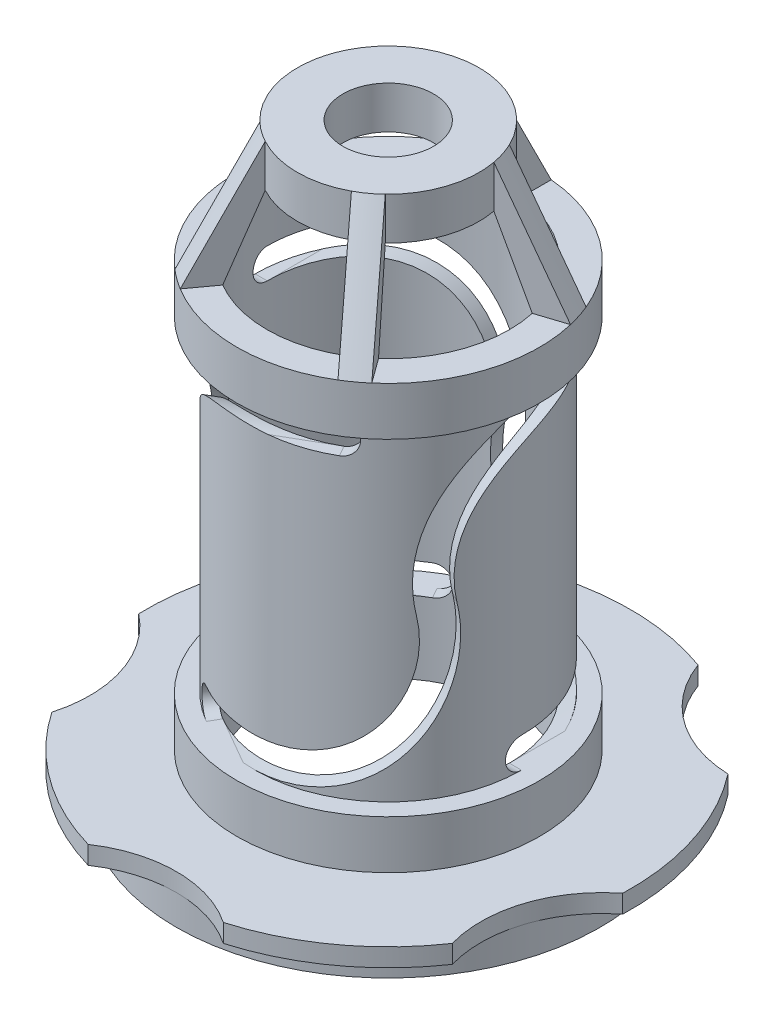
SolidWorks part; units mm, degrees
ref_plane "前视基准面" through (0, 0, 0) normal (0, 0, 1) x (1, 0, 0)
ref_plane "上视基准面" through (0, 0, 0) normal (0, 1, 0) x (1, 0, 0)
ref_plane "右视基准面" through (0, 0, 0) normal (1, 0, 0) x (0, 0, -1)
other "Configuration Table"
sketch "草图1" plane through (0, 0, 0) normal (0, 0, 1) x (1, 0, 0)
  line L0 (0, 74.4543) -> (0, -61.1877) construction
  line L2 (35, -49) -> (35, -44)
  line L3 (35, -44) -> (40, -44)
  line L4 (40, -44) -> (40, -41)
  line L5 (40, -41) -> (25, -41)
  line L9 (20, -49) -> (20, 29)
  line L11 (7.5, 49) -> (7.5, 42)
  line L14 (15, 49) -> (7.5, 49)
  line L18 (25, 29) -> (25, 21)
  line L19 (25, 21) -> (22, 21)
  line L20 (22, 21) -> (22, -33)
  line L21 (22, -33) -> (25, -33)
  line L22 (25, -33) -> (25, -41)
  line L23 (35, -49) -> (20, -49)
  line L26 (7.5, 42) -> (15, 42)
  line L27 (15, 42) -> (20, 29)
  line L28 (15, 49) -> (25, 29)
  point P3 (0, 0)
  dimension "D1" = 70
  dimension "D2" = 5
  dimension "D3" = 2
  dimension "D4" = 5
  dimension "D5" = 5
  dimension "D6" = 3
  dimension "D7" = 30
  dimension "D8" = 20
  dimension "D9" = 20
  dimension "D10" = 15
  dimension "D11" = 70
  dimension "D13" = 49
  dimension "D14" = 5
  dimension "D15" = 8
  dimension "D16" = 7
  dimension "D17" = 8
revolve "旋转1" add sketch "草图1" angle 360 about L0
sketch "草图6" plane through (0, -41, 0) normal (0, 1, 0) x (1, 0, 0)
  line L0 (0, 0) -> (0, -84.7171) construction
  line L1 (0, 0) -> (-80.5708, -26.179) construction
  line L2 (0, 0) -> (-49.7955, 68.5376) construction
  line L3 (0, 0) -> (49.7955, 68.5376) construction
  line L4 (0, 0) -> (80.5708, -26.179) construction
  arc A0 (-11.1688, -38.4091) -> (11.1688, -38.4091) centre (0, -55) cw
  circle A1 centre (0, 0) radius 40 construction
  circle A3 centre (0, 0) radius 40 construction
  arc A4 (-11.1688, -38.4091) -> (11.1688, -38.4091) centre (0, 0) ccw
  arc A5 (-39.9806, -1.2469) -> (-33.0779, -22.4912) centre (0, 0) ccw
  arc A6 (-39.9806, -1.2469) -> (-33.0779, -22.4912) centre (-52.3081, -16.9959) cw
  arc A7 (-13.5406, 37.6385) -> (-31.612, 24.5088) centre (0, 0) ccw
  arc A8 (-13.5406, 37.6385) -> (-31.612, 24.5088) centre (-32.3282, 44.4959) cw
  arc A9 (31.612, 24.5088) -> (13.5406, 37.6385) centre (0, 0) ccw
  arc A10 (31.612, 24.5088) -> (13.5406, 37.6385) centre (32.3282, 44.4959) cw
  arc A11 (33.0779, -22.4912) -> (39.9806, -1.2469) centre (0, 0) ccw
  arc A12 (33.0779, -22.4912) -> (39.9806, -1.2469) centre (52.3081, -16.9959) cw
  circle A13 centre (0, 0) radius 35 construction
  point P30 (0, 0)
  dimension "D1" = 20
  dimension "D2" = 5
extrude "切除-拉伸3" cut sketch "草图6" against normal through all
sketch "草图12" plane through (0, 49, 0) normal (0, 1, 0) x (1, 0, 0)
  line L0 (0, 0) -> (0, 44.7036) construction
  line L1 (-2, 24.9199) -> (-2, 14.8661)
  line L2 (2, 24.9199) -> (2, 14.8661)
  line L3 (23.0822, 9.6028) -> (13.5204, 6.496)
  line L4 (24.3182, 5.7986) -> (14.7565, 2.6918)
  line L5 (0, 0) -> (42.5156, 13.8142) construction
  line L6 (16.2656, -18.985) -> (10.3561, -10.8513)
  line L7 (13.0295, -21.3362) -> (7.12, -13.2025)
  line L8 (0, 0) -> (26.2761, -36.166) construction
  line L9 (-13.0295, -21.3362) -> (-7.12, -13.2025)
  line L10 (-16.2656, -18.985) -> (-10.3561, -10.8513)
  line L11 (0, 0) -> (-26.2761, -36.166) construction
  line L12 (-24.3182, 5.7986) -> (-14.7565, 2.6918)
  line L13 (-23.0822, 9.6028) -> (-13.5204, 6.496)
  line L14 (0, 0) -> (-42.5156, 13.8142) construction
  circle A0 centre (0, 0) radius 15 construction
  circle A1 centre (0, 0) radius 25
  arc A2 (23.0822, 9.6028) -> (2, 24.9199) centre (0, 0) ccw
  arc A3 (13.5204, 6.496) -> (2, 14.8661) centre (0, 0) ccw
  arc A4 (10.3561, -10.8513) -> (14.7565, 2.6918) centre (0, 0) ccw
  arc A5 (16.2656, -18.985) -> (24.3182, 5.7986) centre (0, 0) ccw
  arc A6 (-7.12, -13.2025) -> (7.12, -13.2025) centre (0, 0) ccw
  arc A7 (-13.0295, -21.3362) -> (13.0295, -21.3362) centre (0, 0) ccw
  arc A8 (-24.3182, 5.7986) -> (-16.2656, -18.985) centre (0, 0) ccw
  arc A9 (-14.7565, 2.6918) -> (-10.3561, -10.8513) centre (0, 0) ccw
  arc A10 (-2, 24.9199) -> (-23.0822, 9.6028) centre (0, 0) ccw
  arc A11 (-2, 14.8661) -> (-13.5204, 6.496) centre (0, 0) ccw
  point P36 (0, 0)
  dimension "D2" = 4
  dimension "D3" = 5
  dimension "D1" = 0
extrude "切除-拉伸5" cut sketch "草图12" against normal blind 20
sketch "草图13" plane through (0, -49, 0) normal (0, -1, 0) x (1, 0, 0)
  line L1 (31.7404, -10.3131) -> (19.6166, 27)
  line L2 (19.6166, 27) -> (-19.6166, 27)
  line L3 (-19.6166, 27) -> (-31.7404, -10.3131)
  line L4 (-31.7404, -10.3131) -> (0, -33.3738)
  line L5 (0, -33.3738) -> (31.7404, -10.3131)
  circle A0 centre (0, 0) radius 27 construction
  circle A1 centre (0, 0) radius 20 construction
  dimension "D1" = 7
extrude "切除-拉伸6" cut sketch "草图13" against normal blind 4 draft 30
sketch "草图14" plane through (0, 0, 0) normal (0, 0, 1) x (1, 0, 0)
  line L0 (-20, 29) -> (-20, -45) construction
  line L1 (-22, 21) -> (22, 21) construction
  line L2 (20, -45) -> (20, 29) construction
  line L3 (25, -33) -> (-25, -33) construction
  line L4 (22, -33) -> (-22, -33) construction
  line L6 (20, -28) -> (22, -28)
  line L7 (22, -33) -> (22, 21) construction
  line L8 (22, -28) -> (22, -33)
  line L9 (22, -33) -> (20, -33)
  line L10 (-20, 21) -> (-22, 21)
  line L11 (-22, 21) -> (-22, 16)
  line L12 (-22, 21) -> (-22, -33) construction
  line L13 (-22, 16) -> (-20, 16)
  arc A0 (-20, 21) -> (2.4494, -6.5005) centre (-20, -1.9133) cw
  arc A1 (20, -33) -> (-2.4494, -5.4995) centre (20, -10.0867) cw
  arc A2 (-20, 16) -> (-2.4494, -5.4995) centre (-20, -1.9133) cw
  arc A3 (20, -28) -> (2.4494, -6.5005) centre (20, -10.0867) cw
  arc A4 (20, -33) -> (-1.2151, -1.4302) centre (20, -10.0867) cw construction
  arc A5 (-20, 21) -> (-1.7856, -15.8149) centre (-20, -1.9133) cw construction
  arc A6 (-20, 16) -> (-5.7603, -12.7814) centre (-20, -1.9133) cw construction
  arc A7 (20, -28) -> (3.4143, -3.3192) centre (20, -10.0867) cw construction
  dimension "D1" = 5
  dimension "D2" = 5
extrude "切除-拉伸7" cut sketch "草图14" against normal up to next
sketch "草图15" plane through (0, 0, 0) normal (1, 0, 0) x (0, 0, -1)
  line L0 (0, 16) -> (0, 21) construction
  line L1 (-22, 21) -> (22, 21) construction
  line L2 (0, -33) -> (0, -28) construction
  line L3 (0, -28) -> (9.1652, -28) construction
  circle A0 centre (0, 18.5) radius 2.5
  circle A1 centre (0, -30.5) radius 2.5
extrude "切除-拉伸8" cut sketch "草图15" against normal up to next contours A0 region at (0, 18.5, 0)
extrude "切除-拉伸9" cut sketch "草图15<5>" along normal up to next contours A1 region at (0, -30.5, 0)
sketch "草图15<5>" plane through (0, 0, 0) normal (1, 0, 0) x (0, 0, -1) same geometry as "草图15"
pattern_circular "阵列(圆周)2" count 3 over 360 of "切除-拉伸9", "切除-拉伸8", "切除-拉伸7"
